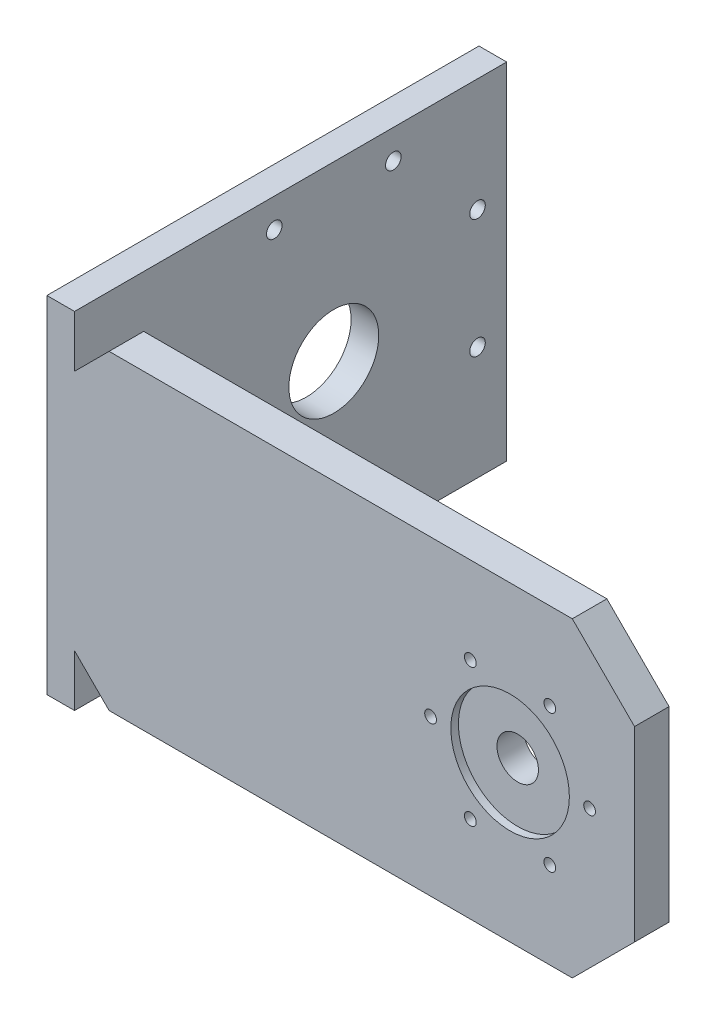
SolidWorks part; units mm, degrees
ref_plane "Front Plane" through (0, 0, 0) normal (0, 0, 1) x (1, 0, 0)
ref_plane "Top Plane" through (0, 0, 0) normal (0, 1, 0) x (1, 0, 0)
ref_plane "Right Plane" through (0, 0, 0) normal (1, 0, 0) x (0, 0, -1)
ref_plane "PL_Top_Plate_base" through (0, 0, 65) normal (0, 0, 1) x (1, 0, 0)
sketch "SK_Top_Plate" plane through (0, 0, 65) normal (0, 0, 1) x (1, 0, 0)
  line L0 (-116, -45) -> (18, -45)
  line L1 (18, -45) -> (36, -27)
  line L2 (36, -27) -> (36, 27)
  line L3 (36, 27) -> (18, 45)
  line L4 (18, 45) -> (-116, 45)
  line L5 (-116, 45) -> (-134, 27)
  line L6 (-134, 27) -> (-134, -27)
  line L7 (-134, -27) -> (-116, -45)
  circle A0 centre (23, 0) radius 1.7
  circle A1 centre (11.5, 19.9186) radius 1.7
  circle A2 centre (-11.5, 19.9186) radius 1.7
  circle A3 centre (-23, 0) radius 1.7
  circle A4 centre (-11.5, -19.9186) radius 1.7
  circle A5 centre (11.5, -19.9186) radius 1.7
  circle A6 centre (0, 0) radius 6
  dimension "D17_SK_Top_Plate" = 3.4
  dimension "D19_SK_Top_Plate" = 3.4
  dimension "D22_SK_Top_Plate" = 3.4
  dimension "D25_SK_Top_Plate" = 3.4
  dimension "D27_SK_Top_Plate" = 3.4
  dimension "D30_SK_Top_Plate" = 3.4
  dimension "D33_SK_Top_Plate" = 12
  dimension "P1" = 116
  dimension "P2" = 45
  dimension "P3" = 18
  dimension "P4" = 45
  dimension "P5" = 36
  dimension "P6" = 27
  dimension "P7" = 36
  dimension "P8" = 27
  dimension "P9" = 18
  dimension "P10" = 45
  dimension "P11" = 116
  dimension "P12" = 45
  dimension "P13" = 134
  dimension "P14" = 27
  dimension "P15" = 134
  dimension "P16" = 27
  dimension "P18" = 23
  dimension "P20" = 11.5
  dimension "P21" = 19.9186
  dimension "P23" = 11.5
  dimension "P24" = 19.9186
  dimension "P26" = 23
  dimension "P28" = 11.5
  dimension "P29" = 19.9186
  dimension "P31" = 11.5
  dimension "P32" = 19.9186
extrude "Top_Plate" add sketch "SK_Top_Plate" along normal blind 10
ref_plane "PL_Yaw_Pilot_Recess_base" through (0, 0, 75) normal (0, 0, 1) x (1, 0, 0)
sketch "SK_Yaw_Pilot_Recess" plane through (0, 0, 75) normal (0, 0, 1) x (1, 0, 0)
  circle A0 centre (0, 0) radius 17.15
  dimension "D1_SK_Yaw_Pilot_Recess" = 34.3
extrude "Yaw_Pilot_Recess" cut sketch "SK_Yaw_Pilot_Recess" against normal blind 2.2
ref_plane "PL_Back_Plate_base" through (-134, 0, 0) normal (1, 0, 0) x (0, 0, -1)
sketch "SK_Back_Plate" plane through (-134, 0, 0) normal (1, 0, 0) x (0, 0, -1)
  line L0 (50, -50) -> (50, 50)
  line L1 (50, 50) -> (-75, 50)
  line L2 (-75, 50) -> (-75, -50)
  line L3 (-75, -50) -> (50, -50)
  circle A0 centre (41.5746, 17.2208) radius 2.25
  circle A1 centre (17.2208, 41.5746) radius 2.25
  circle A2 centre (-17.2208, 41.5746) radius 2.25
  circle A3 centre (-41.5746, 17.2208) radius 2.25
  circle A4 centre (-41.5746, -17.2208) radius 2.25
  circle A5 centre (-17.2208, -41.5746) radius 2.25
  circle A6 centre (17.2208, -41.5746) radius 2.25
  circle A7 centre (41.5746, -17.2208) radius 2.25
  circle A8 centre (0, 0) radius 13
  dimension "D9_SK_Back_Plate" = 4.5
  dimension "D12_SK_Back_Plate" = 4.5
  dimension "D15_SK_Back_Plate" = 4.5
  dimension "D18_SK_Back_Plate" = 4.5
  dimension "D21_SK_Back_Plate" = 4.5
  dimension "D24_SK_Back_Plate" = 4.5
  dimension "D27_SK_Back_Plate" = 4.5
  dimension "D30_SK_Back_Plate" = 4.5
  dimension "D33_SK_Back_Plate" = 26
  dimension "P1" = 50
  dimension "P2" = 50
  dimension "P3" = 50
  dimension "P4" = 50
  dimension "P5" = 75
  dimension "P6" = 50
  dimension "P7" = 75
  dimension "P8" = 50
  dimension "P10" = 41.5746
  dimension "P11" = 17.2208
  dimension "P13" = 17.2208
  dimension "P14" = 41.5746
  dimension "P16" = 17.2208
  dimension "P17" = 41.5746
  dimension "P19" = 41.5746
  dimension "P20" = 17.2208
  dimension "P22" = 41.5746
  dimension "P23" = 17.2208
  dimension "P25" = 17.2208
  dimension "P26" = 41.5746
  dimension "P28" = 17.2208
  dimension "P29" = 41.5746
  dimension "P31" = 41.5746
  dimension "P32" = 17.2208
extrude "Back_Plate" add sketch "SK_Back_Plate" along normal blind 8
ref_plane "PL_Rib_base" through (0, -4, 0) normal (0, 1, 0) x (1, 0, 0)
sketch "SK_Rib" plane through (0, -4, 0) normal (0, 1, 0) x (1, 0, 0)
  line L0 (-134, -52) -> (-30, -65)
  line L1 (-30, -65) -> (-134, -65)
  line L2 (-134, -65) -> (-134, -52)
  dimension "P1" = 134
  dimension "P2" = 52
  dimension "P3" = 30
  dimension "P4" = 65
  dimension "P5" = 134
  dimension "P6" = 65
extrude "Rib" add sketch "SK_Rib" along normal blind 8
equation "\"Yaw_face_z\" = 75"
equation "\"Roll_rear_x\" = -126"
